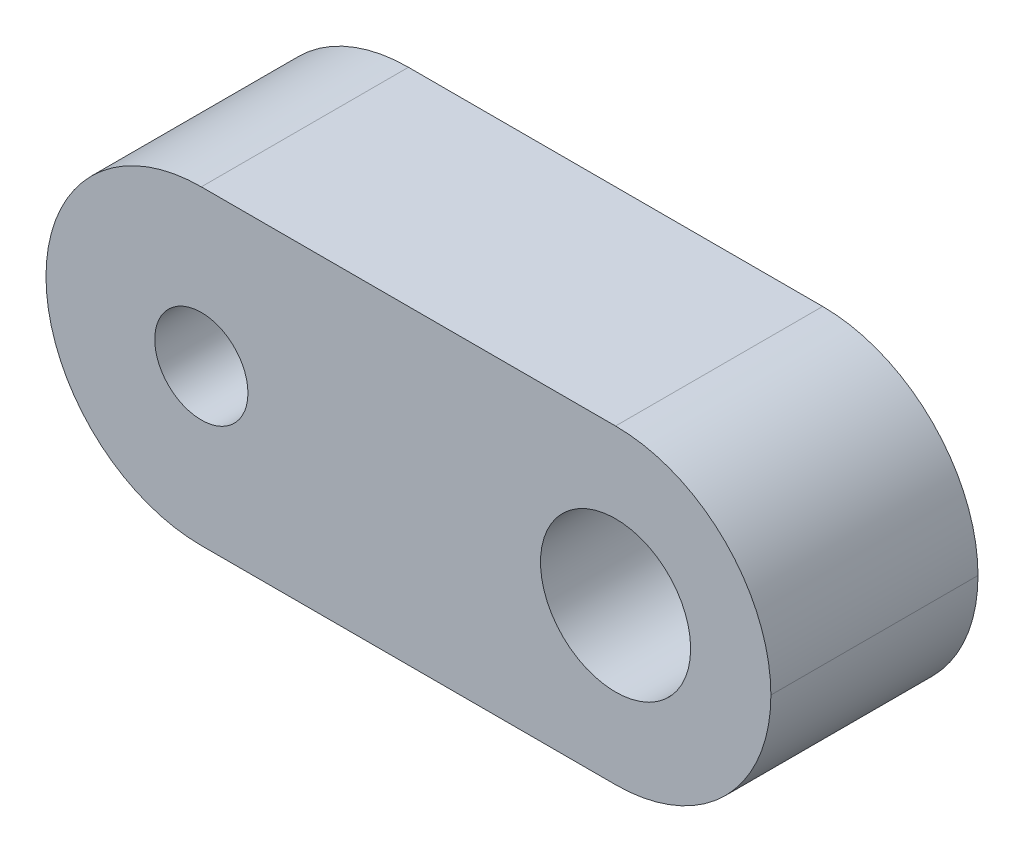
SolidWorks part; units mm, degrees
ref_plane "Front" through (0, 0, 0) normal (0, 0, 1) x (1, 0, 0)
ref_plane "Top" through (0, 0, 0) normal (0, 1, 0) x (1, 0, 0)
ref_plane "Right" through (0, 0, 0) normal (1, 0, 0) x (0, 0, -1)
sketch "Sketch1" plane through (0, 0, 0) normal (0, 0, 1) x (1, 0, 0)
  line L1 (0, 0) -> (14, 0)
  line L2 (0, 0) -> (0, -6)
  line L3 (0, -6) -> (14, -6)
  line L4 (14, 0) -> (14, -6)
  dimension "D1" = 6
  dimension "D2" = 14
extrude "Boss-Extrude1" add sketch "Sketch1" along normal blind 4
sketch "Sketch2" plane through (0, 0, 4) normal (0, 0, 1) x (1, 0, 0)
  line L0 (0, 0) -> (0, -6) construction
  line L1 (14, -6) -> (14, 0) construction
  circle A0 centre (3, -3) radius 0.9
  circle A1 centre (11, -3) radius 1.45
  dimension "D1" = 1.8
  dimension "D3" = 2.9
  dimension "D2" = 3
  dimension "D4" = 3
extrude "Cut-Extrude1" cut sketch "Sketch2" against normal through all and the other way through all
fillet "Fillet1" radius 3 4 edges at (14, -6, 2) (14, 0, 2) (0, -6, 2) (0, 0, 2)
